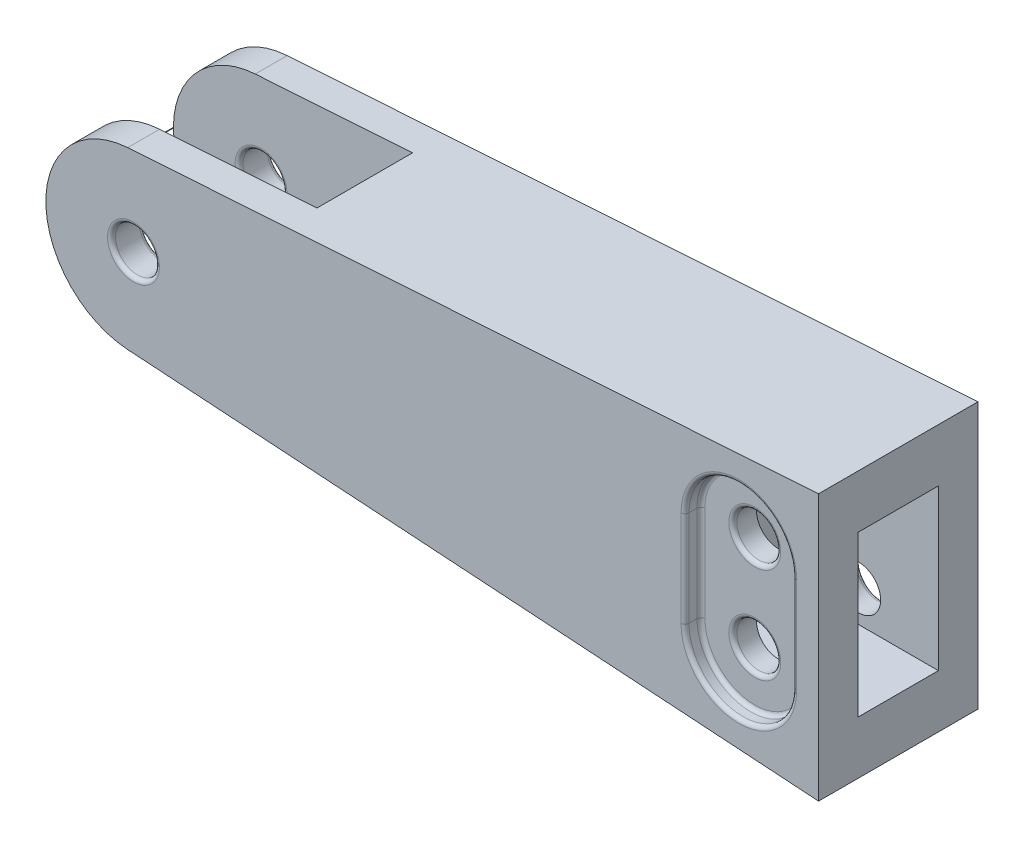
SolidWorks part; units mm, degrees
ref_plane "Front Plane" through (0, 0, 0) normal (0, 0, 1) x (1, 0, 0)
ref_plane "Top Plane" through (0, 0, 0) normal (0, 1, 0) x (1, 0, 0)
ref_plane "Right Plane" through (0, 0, 0) normal (1, 0, 0) x (0, 0, -1)
sketch "Sketch1" plane through (0, 0, 0) normal (0, 0, 1) x (1, 0, 0)
  line L1 (43.0973, 0) -> (50043.0973, 0) construction
  line L2 (0, 21.9801) -> (0, 50021.9801) construction
  line L5 (-147.5823, 10.9687) -> (-60.9241, 16.6957)
  line L6 (-60.9241, -16.6957) -> (-17.5184, -19.5642) construction
  line L7 (-60.9241, 16.6957) -> (-60.9241, -16.6957) construction
  line L8 (-60.9241, 16.6957) -> (-60.9241, -16.6957)
  line L9 (-147.5823, -10.9687) -> (-60.9241, -16.6957)
  arc A1 (-147.5823, 10.9687) -> (-147.5823, -10.9687) centre (-146.8574, 0) ccw
  point P9 (0, 0)
  dimension "D1" = 146.8574
extrude "Boss-Extrude1" add sketch "Sketch1" along normal up to surface (20 mm away) contours A1 region at (-104.6889, 0, 0)
sketch "Sketch2" plane through (-60.9241, 0, 0) normal (1, 0, 0) x (0, 0, -1)
  line L0 (-10, -16.6957) -> (-10, 16.6957) construction
  line L4 (-15.035, -10.035) -> (-4.965, -10.035)
  line L5 (-15.035, -10.035) -> (-15.035, 10.035)
  line L6 (-15.035, 10.035) -> (-4.965, 10.035)
  line L7 (-20, -16.6957) -> (0, -16.6957)
  line L13 (-20, 16.6957) -> (-20, -16.6957)
  line L14 (0, 16.6957) -> (-20, 16.6957)
  line L15 (0, -16.6957) -> (0, 16.6957)
  line L16 (-20, -16.6957) -> (0, -16.6957) construction
  line L17 (-20, 16.6957) -> (-20, -16.6957) construction
  line L18 (0, 16.6957) -> (-20, 16.6957) construction
  line L19 (0, -16.6957) -> (0, 16.6957) construction
  line L20 (-4.965, -10.035) -> (-4.965, 10.035)
  line L21 (-15.035, -10.035) -> (-4.965, 10.035) construction
  line L22 (-15.035, 10.035) -> (-4.965, -10.035) construction
  line L23 (0, 0) -> (-20, 0) construction
  point P2 (-10, 0)
  point P15 (-10, 0)
  dimension "D2" = 10.07
  dimension "D3" = 20.07
  dimension "D1" = 0
extrude "Cut-Extrude1" cut sketch "Sketch2" against normal blind 20
sketch "Sketch4" plane through (0, 0, 0) normal (0, 1, 0) x (1, 0, 0)
  line L0 (-60.9241, -20) -> (-147.5823, -20) construction
  line L5 (-157.85, 0) -> (-157.85, -20) construction
  line L6 (-157.85, -4) -> (-127.85, -4)
  line L7 (-157.85, -4) -> (-157.85, -16)
  line L10 (-157.85, -16) -> (-127.85, -16)
  line L15 (-127.85, -4) -> (-127.85, -16)
  line L16 (-157.85, -4) -> (-127.85, -16) construction
  line L17 (-157.85, -16) -> (-127.85, -4) construction
  line L18 (-147.5823, 0) -> (-157.8501, 0) construction
  point P4 (-142.85, -10)
  dimension "D1" = 4
  dimension "D2" = 4
  dimension "D3" = 30
extrude "Cut-Extrude2" cut sketch "Sketch4" against normal through all both and the other way through all
sketch "Sketch5" plane through (0, 0, 0) normal (0, 0, -1) x (-1, 0, 0)
  circle A0 centre (146.8574, 0) radius 2.75
  dimension "D1" = 5.5
extrude "Cut-Extrude3" cut sketch "Sketch5" against normal through all
sketch "Sketch6" plane through (0, 0, 0) normal (0, 0, -1) x (-1, 0, 0)
  line L1 (0, 0) -> (50000, 0) construction
  line L2 (60.9241, 16.6957) -> (60.9241, -16.6957) construction
  circle A0 centre (70.9241, -6) radius 2.75
  circle A1 centre (70.9241, 6) radius 2.75
  dimension "D1" = 5.5
  dimension "D2" = 10
  dimension "D3" = 6
extrude "Cut-Extrude4" cut sketch "Sketch6" against normal through all
sketch "Sketch8" plane through (0, 0, 0) normal (0, 0, -1) x (-1, 0, 0)
  line L0 (64.1741, 6) -> (64.1741, -6)
  line L2 (77.6741, 6) -> (77.6741, -6)
  circle A0 centre (70.9241, -6) radius 2.75 construction
  circle A1 centre (70.9241, 6) radius 2.75 construction
  circle A2 centre (70.9241, -6) radius 2.75 construction
  circle A3 centre (70.9241, 6) radius 2.75 construction
  arc A4 (64.1741, -6) -> (77.6741, -6) centre (70.9241, -6) ccw
  arc A5 (77.6741, 6) -> (64.1741, 6) centre (70.9241, 6) ccw
  circle A6 centre (70.9241, 6) radius 6.75 construction
  circle A7 centre (70.9241, -6) radius 6.75 construction
  dimension "D1" = 4
extrude "Cut-Extrude5" cut sketch "Sketch8" against normal blind 2
ref_plane "Plane1" through (0, 0, 10) normal (0, 0, -1) x (-1, 0, 0)
mirror "Mirror1" about plane through (0, 0, 10) normal (0, 0, -1) of "Cut-Extrude5"
fillet "Fillet2" radius 0.5 24 edges at (-70.9241, -12.75, 2) (-64.1741, 0, 2) (-70.9241, 12.75, 2) (-70.9241, -12.75, 0) (-64.1741, 0, 0) (-70.9241, 12.75, 0) (-70.9241, -12.75, 18) (-64.1741, 0, 18) (-70.9241, 12.75, 18) (-70.9241, -12.75, 20) (-64.1741, 0, 20) (-70.9241, 12.75, 20) (-149.6074, 0, 4) (-149.6074, 0, 0) (-144.1074, 0, 16) (-149.6074, 0, 20) (-68.1741, -6, 18) (-68.1741, 6, 18) (-73.6741, -6, 2) (-73.6741, 6, 2) (-77.6741, 0, 18) (-77.6741, 0, 20) (-77.6741, 0, 2) (-77.6741, 0, 0)
